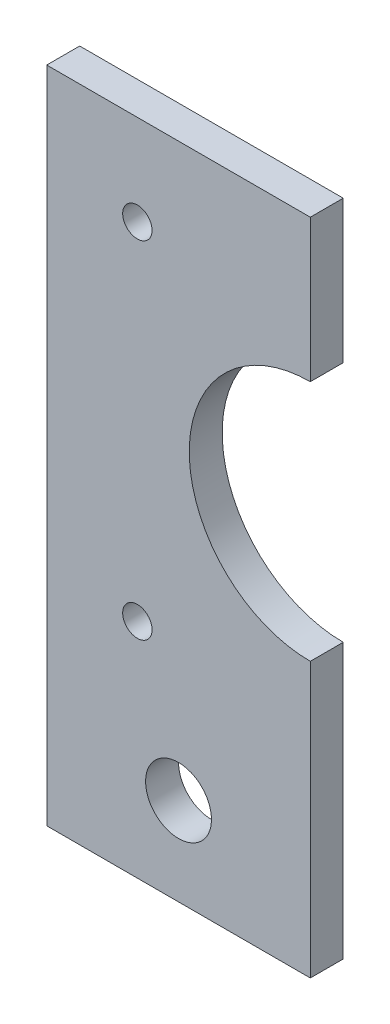
SolidWorks part; units mm, degrees
ref_plane "Front Plane" through (0, 0, 0) normal (0, 0, 1) x (1, 0, 0)
ref_plane "Top Plane" through (0, 0, 0) normal (0, 1, 0) x (1, 0, 0)
ref_plane "Right Plane" through (0, 0, 0) normal (1, 0, 0) x (0, 0, -1)
sketch "Sketch2" plane through (0, 0, 0) normal (0, 0, 1) x (1, 0, 0)
  line L1 (0, 38.1) -> (-38.1, 38.1)
  line L2 (0, 38.1) -> (0, -57.15)
  line L3 (0, -57.15) -> (-38.1, -57.15)
  line L4 (-38.1, 38.1) -> (-38.1, -57.15)
  dimension "D1" = 38.1
  dimension "D2" = 95.25
  dimension "D3" = 38.1
extrude "Boss-Extrude1" add sketch "Sketch2" along normal blind 4.7625
sketch "Sketch3" plane through (0, 0, 0) normal (0, 0, 1) x (1, 0, 0)
  line L0 (0, -57.15) -> (-38.1, -57.15) construction
  circle A0 centre (0, 0) radius 17.5
  circle A1 centre (-25, 25) radius 2.125
  circle A2 centre (25, 25) radius 2.125
  circle A3 centre (25, -25) radius 2.125
  circle A4 centre (-25, -25) radius 2.125
  circle A5 centre (-19.05, -44.45) radius 4.7625
  point P2 (-25, -25)
  point P5 (25, -25)
  point P12 (25, 25)
  point P15 (-25, 25)
  point P17 (25, 25)
  point P19 (0, 0)
  point P21 (-19.05, -57.15)
  point P22 (-19.05, -41.1457)
  dimension "D3" = 25
  dimension "D5" = 4.25
  dimension "D6" = 35
  dimension "D8" = 9.525
  dimension "D1" = 50
  dimension "D2" = 50
  dimension "D4" = 25
  dimension "D7" = 12.7
extrude "Cut-Extrude3" cut sketch "Sketch3" along normal through all
